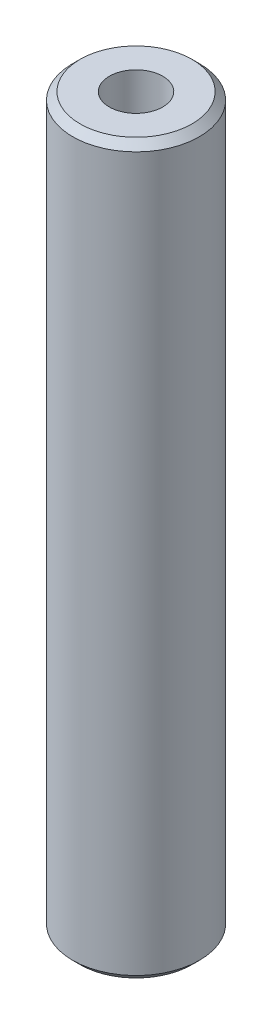
SolidWorks part; units mm, degrees
ref_plane "Front Plane" through (0, 0, 0) normal (0, 0, 1) x (1, 0, 0)
ref_plane "Top Plane" through (0, 0, 0) normal (0, 1, 0) x (1, 0, 0)
ref_plane "Right Plane" through (0, 0, 0) normal (1, 0, 0) x (0, 0, -1)
sketch "Sketch1" plane through (0, 0, 0) normal (0, 1, 0) x (1, 0, 0)
  circle A0 centre (0, 0) radius 5
  dimension "SHAFT_OD" = 10
extrude "Boss-Extrude1" add sketch "Sketch1" along normal blind 57.452
sketch "Sketch2" plane through (0, 0, 0) normal (0, 1, 0) x (1, 0, 0)
  circle A0 centre (0, 0) radius 2.1069
  dimension "BORE_D" = 4.2138
extrude "Cut-Extrude1" cut sketch "Sketch2" along normal through all
chamfer "Chamfer1" distance 0.5851 angle 45 2 edges at (0, 57.452, 5) (0, 0, 5)
